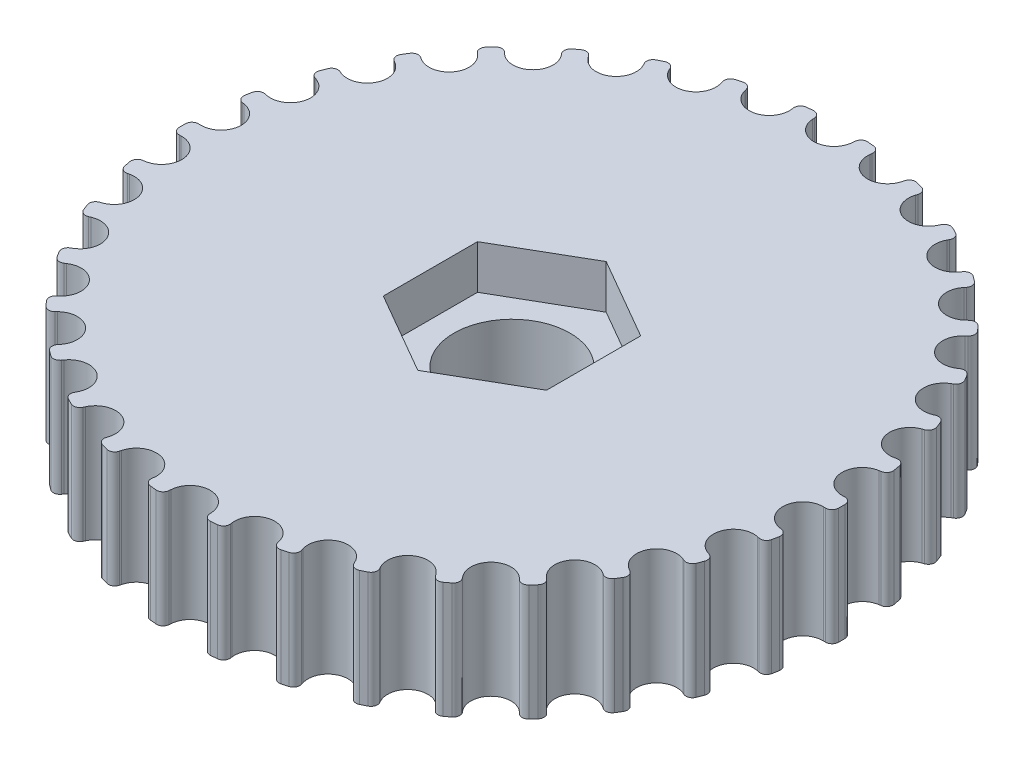
SolidWorks part; units mm, degrees
ref_plane "Front Plane" through (0, 0, 0) normal (0, 0, 1) x (1, 0, 0)
ref_plane "Top Plane" through (0, 0, 0) normal (0, 1, 0) x (1, 0, 0)
ref_plane "Right Plane" through (0, 0, 0) normal (1, 0, 0) x (0, 0, -1)
sketch "Эскиз1" plane through (0, 0, 0) normal (0, 1, 0) x (1, 0, 0)
  circle A5 centre (0, 0) radius 25.55
  dimension "D1" = 51.1
extrude "Бобышка-Вытянуть1" add sketch "Эскиз1" along normal blind 9 contours A5 region at (0, 0, 0)
sketch "Эскиз2" plane through (0, 9, 0) normal (0, 1, 0) x (1, 0, 0)
  circle A0 centre (0, 0) radius 4.5
  dimension "D1" = 9
extrude "Вырез-Вытянуть1" cut sketch "Эскиз2" against normal through all
sketch "Эскиз3" plane through (0, 9, 0) normal (0, 1, 0) x (1, 0, 0)
  line L1 (0, 7.3) -> (-6.322, 3.65)
  line L2 (-6.322, 3.65) -> (-6.322, -3.65)
  line L3 (-6.322, -3.65) -> (0, -7.3)
  line L4 (0, -7.3) -> (6.322, -3.65)
  line L5 (6.322, -3.65) -> (6.322, 3.65)
  line L6 (6.322, 3.65) -> (0, 7.3)
  circle A0 centre (0, 0) radius 6.322 construction
  dimension "D1" = 14.6
extrude "Вырез-Вытянуть2" cut sketch "Эскиз3" against normal blind 3.4
sketch "Эскиз4" plane through (0, 9, 0) normal (0, 1, 0) x (1, 0, 0)
  line L0 (0, 0) -> (-2.0263, 32.3445)
  line L1 (-2.0263, 32.3445) -> (2.0263, 32.3445)
  line L2 (2.0263, 32.3445) -> (0, 0)
  circle A0 centre (0, 0) radius 25.55
  circle A1 centre (0, 0) radius 23.39
  circle A2 centre (0, 24.95) radius 1.56
  circle M7 centre (0, 0) radius 25.55
  dimension "D1" = 46.78
  dimension "D2" = 51.1
  dimension "D3" = 3.12
extrude "Вырез-Вытянуть3" cut sketch "Эскиз4" against normal blind 10 contours A2 A0 | A2 L2 M7 | A2 L0 M7 region at (-1.5455, 9, -25.3422) region at (0, 9, -24.5909) region at (1.5455, 9, -25.3422)
fillet "Скругление1" radius 0.5 2 edges at (-1.5975, 4.5, -25.5) (1.5975, 4.5, -25.5)
pattern_circular "Круговой массив1" count 34 over 360 about axis through (0, 0, 0) along (0, 1, 0) of "Скругление1", "Вырез-Вытянуть3" reverse direction yes
